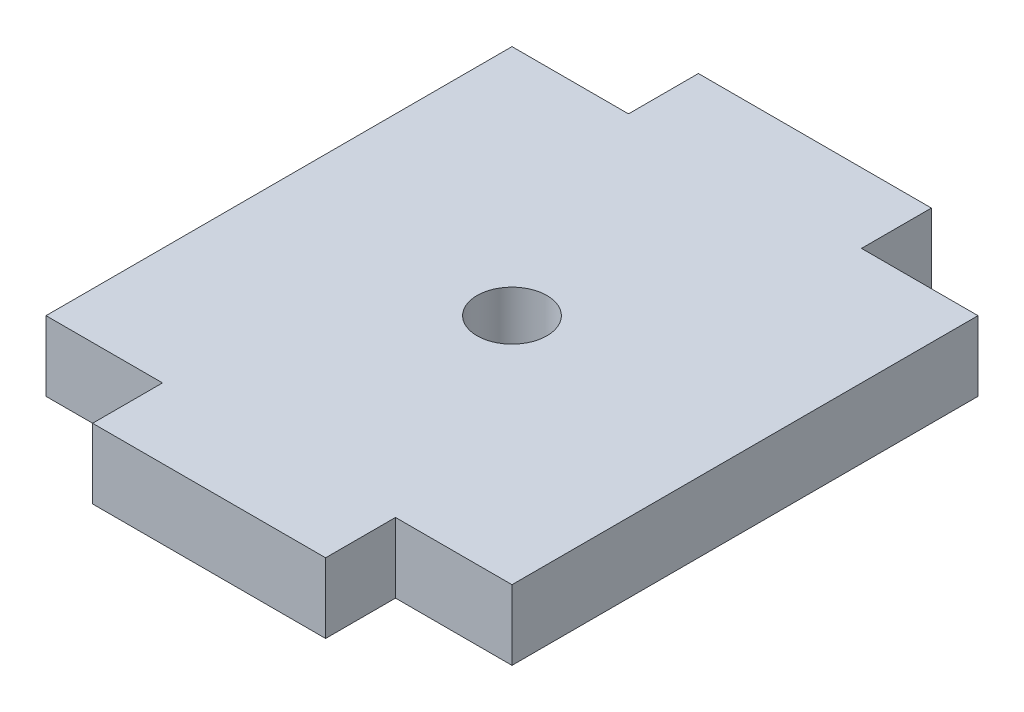
SolidWorks part; units mm, degrees
ref_plane "Front Plane" through (0, 0, 0) normal (0, 0, 1) x (1, 0, 0)
ref_plane "Top Plane" through (0, 0, 0) normal (0, 1, 0) x (1, 0, 0)
ref_plane "Right Plane" through (0, 0, 0) normal (1, 0, 0) x (0, 0, -1)
sketch "Sketch1" plane through (0, 0, 0) normal (0, 1, 0) x (1, 0, 0)
  line L0 (15, 20) -> (20, 20)
  line L5 (0, 0) -> (5, 0)
  line L6 (0, 0) -> (0, 20)
  line L7 (0, 20) -> (5, 20)
  line L8 (20, 0) -> (20, 20)
  line L18 (5, 20) -> (5, 23)
  line L19 (5, 23) -> (15, 23)
  line L20 (15, 20) -> (15, 23)
  line L22 (5, 0) -> (5, -3)
  line L23 (5, -3) -> (15, -3)
  line L24 (15, 0) -> (15, -3)
  line L25 (15, 0) -> (20, 0)
  line L26 (10, 23) -> (10, -3) construction
  line L27 (0, 10) -> (20, 10) construction
  circle A0 centre (10, 10) radius 1.5
  dimension "D1" = 3
  dimension "D2" = 10
  dimension "D3" = 20
  dimension "D4" = 20
  dimension "D5" = 5
  dimension "D6" = 5
  dimension "D7" = 10
  dimension "D8" = 3
extrude "Boss-Extrude2" add sketch "Sketch1" along normal blind 3
